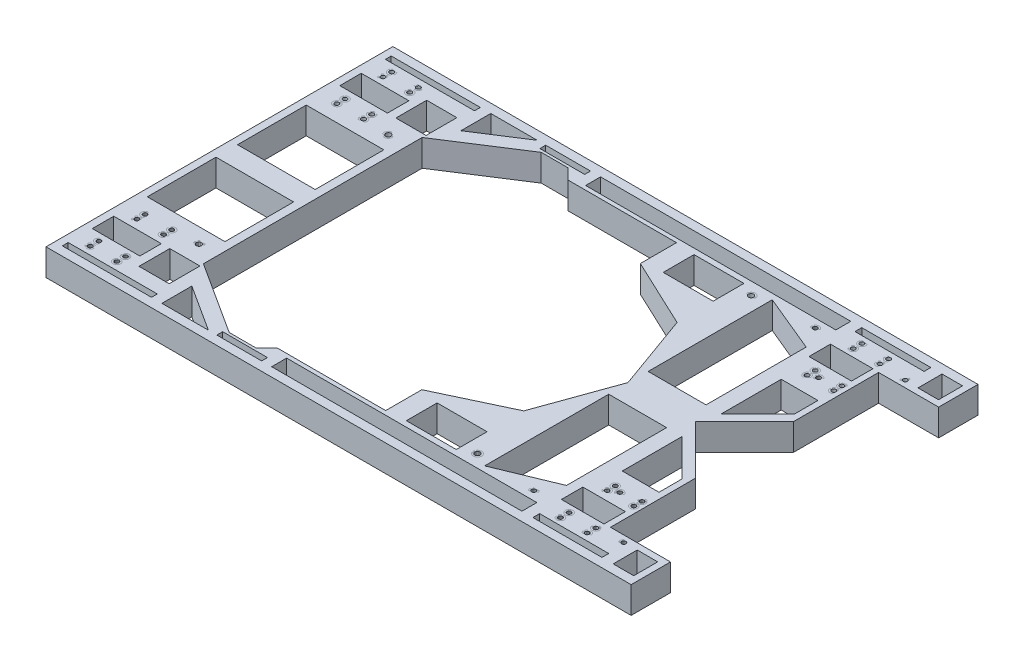
SolidWorks part; units mm, degrees
material "Magnesium Alloy"
ref_plane "Front Plane" through (0, 0, 0) normal (0, 0, 1) x (1, 0, 0)
ref_plane "Top Plane" through (0, 0, 0) normal (0, 1, 0) x (1, 0, 0)
ref_plane "Right Plane" through (0, 0, 0) normal (1, 0, 0) x (0, 0, -1)
sketch "Sketch1" plane through (0, 0, 0) normal (0, 1, 0) x (1, 0, 0)
  line L0 (0, 471.9498) -> (0, -504.9384) construction
  line L1 (-300.0375, 165.1) -> (300.0375, 165.1)
  line L2 (-300.0375, 165.1) -> (-300.0375, -165.1)
  line L3 (-300.0375, -165.1) -> (300.0375, -165.1)
  line L4 (300.0375, 165.1) -> (300.0375, -165.1)
  line L5 (-636.3607, 0) -> (748.0963, 0) construction
  dimension "D1" = 600.075
  dimension "D2" = 330.2
extrude "Boss-Extrude1" add sketch "Sketch1" along normal blind 25.4
sketch "Sketch2" plane through (-300.0375, 0, 0) normal (-1, 0, 0) x (0, 0, 1)
  line L0 (-165.1, 12.7) -> (165.1, 12.7) construction
  line L1 (-165.1, 25.4) -> (-165.1, 0) construction
  line L2 (165.1, 25.4) -> (165.1, 0) construction
  text T0 "Back" font "Century Gothic" height 19.05
extrude "Cut-Extrude1" cut sketch "Sketch2" against normal blind 2.54
sketch "Sketch3" plane through (300.0375, 0, 0) normal (1, 0, 0) x (0, 0, -1)
  line L0 (-165.1, 12.7) -> (165.1, 12.7) construction
  line L1 (-165.1, 25.4) -> (-165.1, 0) construction
  line L2 (165.1, 25.4) -> (165.1, 0) construction
  text T0 "Front" font "Century Gothic" height 19.05
extrude "Cut-Extrude2" cut sketch "Sketch3" against normal blind 2.54
sketch "Sketch4" plane through (0, 0, 0) normal (0, -1, 0) x (1, 0, 0)
  line L0 (407.1831, 0) -> (-551.8052, 0) construction
  line L1 (-113.3475, 138.43) -> (39.6875, 138.43)
  line L2 (-113.3475, 138.43) -> (-113.3475, -138.43)
  line L3 (-113.3475, -138.43) -> (39.6875, -138.43)
  line L4 (39.6875, 138.43) -> (39.6875, -138.43)
  line L5 (60.0798, 0) -> (-60.0798, 0) construction
  line L6 (-300.0375, -165.1) -> (-300.0375, 165.1) construction
  line L7 (300.0375, 165.1) -> (300.0375, -165.1) construction
  line L10 (-300.0375, 165.1) -> (300.0375, 165.1) construction
  dimension "D1" = 186.69
  dimension "D2" = 260.35
  dimension "D3" = 26.67
extrude "Cut-Extrude3" cut sketch "Sketch4" against normal up to next
ref_plane "Plane1" through (223.8375, 0, 0) normal (1, 0, 0) x (0, 0, -1)
ref_plane "Plane2" through (-223.8375, 0, 0) normal (-1, 0, 0) x (0, 0, 1)
sketch "Sketch7" plane through (0, 25.4, 0) normal (0, 1, 0) x (1, 0, 0)
  line L0 (-300.0375, -29.6562) -> (-300.0375, -165.1) construction
  line L1 (-300.0375, -165.1) -> (300.0375, -165.1) construction
  point P0 (-236.5375, -91.2978)
  point P1 (-236.5375, -135.2474)
  point P2 (-211.1375, -135.2474)
  point P3 (-211.1375, -91.2978)
  dimension "D1" = 63.5
  dimension "D2" = 63.5
  dimension "D3" = 88.9
  dimension "D4" = 88.9
  dimension "D5" = 29.8526
  dimension "D6" = 29.8526
  dimension "D7" = 43.9496
  dimension "D8" = 43.9496
hole_wizard "#21 (0.159) Diameter Hole1" positions "Sketch10" profile "Sketch11" hole size "#21" standard "ANSI Inch" end condition through all
sketch "Sketch10" plane through (0, 25.4, 0) normal (0, 1, 0) x (1, 0, 0)
  point P0 (-236.5375, -91.2978)
  point P3 (-211.1375, -91.2978)
  point P6 (-211.1375, -135.2474)
  point P9 (-236.5375, -135.2474)
sketch "Sketch11" plane through (-236.5375, 25.4, 91.2978) normal (1, 0, 0) x (0, 0, 1)
  line L0 (0, 0) -> (0, 25.4)
  line L1 (0, 25.4) -> (2.0193, 25.4)
  line L2 (2.0193, 25.4) -> (2.0193, 0)
  line L5 (2.0193, 0) -> (0, 0)
  line L11 (0, -6.35) -> (0, 107.95) construction
  dimension "Thru Hole Dia." = 4.0386
  dimension "Thru Hole Depth" = 25.4
mirror "Mirror3" about plane through (0, 0, 0) normal (1, 0, 0) of "#21 (0.159) Diameter Hole1"
mirror "Mirror4" about plane through (0, 0, 0) normal (0, 0, 1) of "Mirror3"
ref_axis "Axis1" through (-236.5375, 0, 91.2978) along (0, 1, 0)
ref_axis "Axis2" through (-211.1375, 0, 91.2978) along (0, 1, 0)
ref_axis "Axis3" through (-211.1375, 0, 135.2474) along (0, 1, 0)
ref_axis "Axis4" through (-236.5375, 0, 135.2474) along (0, 1, 0)
sketch "Sketch12" plane through (0, 25.4, 0) normal (0, 1, 0) x (1, 0, 0)
  point P0 (78.8458, -130.175)
ref_plane "Plane3" through (0, 0, 130.175) normal (0, 0, 1) x (1, 0, 0)
sketch "Sketch13" plane through (0, 0, 130.175) normal (0, 0, 1) x (1, 0, 0)
  line L0 (78.8458, 65.775) -> (78.8458, -43.461) construction
hole_wizard "Ø5.0mm Dowel Hole2" positions "Sketch16" profile "Sketch17" hole size "Ø5.0" standard "ANSI Metric" end condition through all
sketch "Sketch16" plane through (0, 25.4, 0) normal (0, 1, 0) x (1, 0, 0)
  circle A0 centre (118.8508, -130.175) radius 2.54
  circle A1 centre (118.8508, 130.175) radius 2.54
  circle A2 centre (-186.3725, 90.17) radius 2.54
  circle A3 centre (-186.3725, -90.17) radius 2.54
  point P3 (118.8508, -130.175)
  point P9 (118.8508, 130.175)
  point P12 (-186.3725, 90.17)
  point P21 (-186.3725, -90.17)
  point P24 (118.8508, -130.175)
sketch "Sketch17" plane through (118.8508, 25.4, 130.175) normal (1, 0, 0) x (0, 0, 1)
  line L0 (0, 0) -> (0, 25.4)
  line L1 (0, 25.4) -> (2.5, 25.4)
  line L2 (2.5, 25.4) -> (2.5, 0)
  line L5 (2.5, 0) -> (0, 0)
  line L11 (0, -6.35) -> (0, 107.95) construction
  dimension "Thru Hole Dia." = 5
  dimension "Thru Hole Depth" = 25.4
sketch "Sketch18" plane through (0, 25.4, 0) normal (0, 1, 0) x (1, 0, 0)
  line L0 (300.0375, 30.4067) -> (300.0375, 165.1) construction
  line L1 (300.0375, 127.635) -> (242.8875, 127.635)
  line L2 (300.0375, 127.635) -> (300.0375, -127.635)
  line L3 (300.0375, -127.635) -> (242.8875, -127.635)
  line L4 (242.8875, 127.635) -> (242.8875, -127.635)
  line L5 (300.0375, 165.1) -> (-300.0375, 165.1) construction
  line L6 (-300.0375, -165.1) -> (300.0375, -165.1) construction
  dimension "D1" = 37.465
  dimension "D2" = 37.465
  dimension "D3" = 57.15
extrude "Cut-Extrude4" cut sketch "Sketch18" against normal up to next
sketch "Sketch19" plane through (0, 25.4, 0) normal (0, -1, 0) x (-1, 0, 0)
  circle A0 centre (-218.7586, 94.615) radius 2.032
  circle A1 centre (-218.7586, 94.615) radius 2.032 construction
  circle A2 centre (-218.7586, -94.615) radius 2.032
  circle A3 centre (-218.7586, -94.615) radius 2.032 construction
  circle A4 centre (-176.2125, 133.985) radius 2.032
  circle A5 centre (-176.2125, 133.985) radius 2.032 construction
  circle A6 centre (-176.2125, -133.985) radius 2.032
  circle A7 centre (-176.2125, -133.985) radius 2.032 construction
extrude "Cut-Extrude5" cut sketch "Sketch19" along normal blind 12.7
ref_axis "Axis5" through (176.2125, 12.7, -133.985) along (0, 1, 0)
ref_axis "Axis6" through (176.2125, 12.7, 133.985) along (0, 1, 0)
ref_axis "Axis7" through (218.7586, 12.7, -94.615) along (0, 1, 0)
ref_axis "Axis8" through (218.7586, 12.7, 94.615) along (0, 1, 0)
sketch "Sketch20" plane through (0, 25.4, 0) normal (0, 1, 0) x (1, 0, 0)
  line L0 (300.0375, 165.1) -> (-300.0375, 165.1) construction
  line L1 (300.0375, 127.635) -> (300.0375, 165.1) construction
  circle A0 centre (236.5375, 143.51) radius 2.0193
  dimension "D1" = 21.59
  dimension "D2" = 63.5
extrude "Cut-Extrude6" cut sketch "Sketch20" against normal up to next
sketch "Sketch21" plane through (0, 25.4, 0) normal (0, 1, 0) x (1, 0, 0)
  line L0 (300.0375, 165.1) -> (-300.0375, 165.1) construction
  line L1 (300.0375, 127.635) -> (300.0375, 165.1) construction
  circle A0 centre (211.1375, 143.51) radius 2.0193
  circle A1 centre (211.1375, 99.06) radius 2.0193
  circle A2 centre (236.5375, 99.06) radius 2.0193
  circle A3 centre (236.5375, 143.51) radius 2.0193 construction
  dimension "D1" = 21.59
  dimension "D2" = 25.4
  dimension "D3" = 4.0386
  dimension "D4" = 44.45
  dimension "D5" = 44.45
  dimension "D6" = 63.5
  dimension "D7" = 4.0386
  dimension "D8" = 25.4
  dimension "D9" = 4.0386
extrude "Cut-Extrude7" cut sketch "Sketch21" against normal up to next
pattern_linear "LPattern1" count 2 spacing 447.675 along (-1, 0, 0) of "Cut-Extrude7", "Cut-Extrude6"
mirror "Mirror5" about plane through (0, 0, 0) normal (0, 0, 1) of "LPattern1"
sketch "Sketch22" plane through (0, 25.4, 0) normal (0, 1, 0) x (1, 0, 0)
  line L0 (300.0375, -165.1) -> (300.0375, -127.635) construction
  line L1 (160.3375, -127.635) -> (300.0375, -127.635) construction
  circle A0 centre (261.9375, -133.985) radius 2.032
  dimension "D1" = 4.064
  dimension "D2" = 38.1
  dimension "D3" = 6.35
extrude "Cut-Extrude8" cut sketch "Sketch22" against normal up to next
mirror "Mirror6" about plane through (0, 0, 0) normal (0, 0, 1) of "Cut-Extrude8"
sketch "Sketch23" plane through (0, 25.4, 0) normal (0, 1, 0) x (1, 0, 0)
  circle A0 centre (-236.5375, 143.51) radius 2.0193
  circle A1 centre (-236.5375, 143.51) radius 3.6068
  circle A2 centre (-211.1375, 143.51) radius 2.0193
  circle A3 centre (-211.1375, 143.51) radius 3.6068
  circle A4 centre (-236.5375, 135.2474) radius 2.0193
  circle A5 centre (-236.5375, 135.2474) radius 3.6068
  circle A6 centre (-211.1375, 135.2474) radius 2.0193
  circle A7 centre (-211.1375, 135.2474) radius 3.6068
  circle A8 centre (-236.5375, 99.06) radius 2.0193
  circle A9 centre (-236.5375, 99.06) radius 3.6068
  circle A10 centre (-236.5375, 91.2978) radius 2.0193
  circle A11 centre (-236.5375, 91.2978) radius 3.6068
  circle A12 centre (-211.1375, 99.06) radius 2.0193
  circle A13 centre (-211.1375, 99.06) radius 3.6068
  circle A14 centre (-211.1375, 91.2978) radius 2.0193
  circle A15 centre (-211.1375, 91.2978) radius 3.6068
  circle A16 centre (-186.3725, 90.17) radius 2.5006
  circle A17 centre (-186.3725, 90.17) radius 4.0881
  circle A18 centre (118.8508, 130.175) radius 2.5006
  circle A19 centre (118.8508, 130.175) radius 4.0881
  circle A20 centre (176.2125, 133.985) radius 2.032
  circle A21 centre (211.1375, 99.06) radius 2.0193
  circle A22 centre (211.1375, 91.2978) radius 2.0193
  circle A23 centre (218.7586, 94.615) radius 2.032
  circle A24 centre (211.1375, 135.2474) radius 2.0193
  circle A25 centre (211.1375, 143.51) radius 2.0193
  circle A26 centre (236.5375, 143.51) radius 2.0193
  circle A27 centre (236.5375, 135.2474) radius 2.0193
  circle A28 centre (236.5375, 99.06) radius 2.0193
  circle A29 centre (236.5375, 91.2978) radius 2.0193
  circle A30 centre (261.9375, 133.985) radius 2.032
  circle A31 centre (176.2125, 133.985) radius 3.6195
  circle A32 centre (211.1375, 143.51) radius 3.6068
  circle A33 centre (211.1375, 135.2474) radius 3.6068
  circle A34 centre (211.1375, 99.06) radius 3.6068
  circle A35 centre (211.1375, 91.2978) radius 3.6068
  circle A36 centre (218.7586, 94.615) radius 3.6195
  circle A37 centre (236.5375, 91.2978) radius 3.6068
  circle A38 centre (236.5375, 99.06) radius 3.6068
  circle A39 centre (236.5375, 135.2474) radius 3.6068
  circle A40 centre (236.5375, 143.51) radius 3.6068
  circle A41 centre (261.9375, 133.985) radius 3.6195
  dimension "D1" = 1.5875
  dimension "D2" = 1.5875
  dimension "D3" = 1.5875
  dimension "D4" = 1.5875
  dimension "D5" = 1.5875
  dimension "D6" = 1.5875
  dimension "D7" = 1.5875
  dimension "D8" = 1.5875
  dimension "D9" = 1.5875
  dimension "D10" = 4.0386
  dimension "D11" = 4.0386
  dimension "D12" = 4.0386
  dimension "D13" = 4.0386
  dimension "D14" = 5.0013
  dimension "D15" = 4.0386
  dimension "D16" = 4.0386
  dimension "D17" = 4.0386
  dimension "D18" = 4.0386
  dimension "D19" = 1.5875
  dimension "D20" = 4.064
  dimension "D21" = 1.5875
  dimension "D22" = 1.5875
  dimension "D23" = 1.5875
  dimension "D24" = 1.5875
  dimension "D25" = 1.5875
  dimension "D26" = 1.5875
  dimension "D27" = 1.5875
  dimension "D28" = 1.5875
  dimension "D29" = 1.5875
  dimension "D30" = 1.5875
  dimension "D31" = 1.5875
  dimension "D32" = 5.0013
  dimension "D33" = 4.0386
  dimension "D34" = 4.0386
  dimension "D35" = 4.064
  dimension "D36" = 4.0386
  dimension "D37" = 4.0386
  dimension "D38" = 4.0386
  dimension "D39" = 4.0386
  dimension "D40" = 4.0386
  dimension "D41" = 4.0386
  dimension "D42" = 4.064
extrude "Boss-Extrude2" add sketch "Sketch23" against normal up to surface (25.4 mm away) separate body up to face at (261.9375, 0, -131.953)
mirror "Mirror9" about plane through (0, 0, 0) normal (0, 0, 1) of bodies 128 130 127 131 125 123 124 126 136 137 139 140 142 141 143 134 135 133 132 138 129
sketch "Sketch24" plane through (0, 25.4, 0) normal (0, 1, 0) x (1, 0, 0)
  line L0 (-256.9969, 165.1) -> (-256.9969, 66.04)
  line L1 (-256.9969, 66.04) -> (-168.0969, 66.04)
  line L2 (-168.0969, 66.04) -> (-168.0969, 104.14)
  line L3 (-168.0969, 104.14) -> (-99.1707, 148.5171)
  line L4 (-99.1707, 148.5171) -> (-73.7707, 148.5171)
  line L5 (-73.7707, 148.5171) -> (-63.6526, 138.43)
  line L6 (-63.6526, 138.43) -> (39.5764, 138.43)
  line L7 (39.5764, 138.43) -> (39.5764, 104.0777)
  line L8 (39.5764, 104.0777) -> (105.7193, 72.9194)
  line L9 (105.7193, 72.9194) -> (131.9374, 0)
  line L10 (176.5339, 0) -> (-283.2885, 0) construction
  line L11 (105.7193, -72.9194) -> (131.9374, 0)
  line L12 (39.5764, -104.0777) -> (105.7193, -72.9194)
  line L13 (39.5764, -138.43) -> (39.5764, -104.0777)
  line L14 (-63.6526, -138.43) -> (39.5764, -138.43)
  line L15 (-73.7707, -148.5171) -> (-63.6526, -138.43)
  line L16 (-99.1707, -148.5171) -> (-73.7707, -148.5171)
  line L17 (-168.0969, -104.14) -> (-99.1707, -148.5171)
  line L18 (-168.0969, -66.04) -> (-168.0969, -104.14)
  line L19 (-256.9969, -66.04) -> (-168.0969, -66.04)
  line L20 (-256.9969, -165.1) -> (-256.9969, -66.04)
  line L21 (-256.9969, 165.1) -> (-300.0375, 165.1)
  line L22 (-300.0375, 165.1) -> (-300.0375, -165.1)
  line L23 (-300.0375, -165.1) -> (-256.9969, -165.1)
  line L24 (242.8875, 46.4819) -> (196.2944, 0)
  line L25 (242.8875, -46.4819) -> (196.2944, 0)
  line L26 (300.0375, 165.1) -> (-300.0375, 165.1) construction
  line L27 (-300.0375, 165.1) -> (-300.0375, -165.1) construction
  line L28 (242.8875, 127.635) -> (242.8875, -127.635) construction
  line L29 (-60.0798, 0) -> (60.0798, 0) construction
  line L30 (242.8875, 46.4819) -> (242.8875, -46.4819)
  dimension "D1" = 88.9
  dimension "D2" = 99.06
  dimension "D3" = 38.1
  dimension "D4" = 25.4
extrude "Cut-Extrude9" cut sketch "Sketch24" against normal blind 25.4
sketch "Sketch25" plane through (0, 25.4, 0) normal (0, 1, 0) x (1, 0, 0)
  line L1 (-256.9969, 66.04) -> (-168.0969, 66.04)
  line L2 (-256.9969, 66.04) -> (-256.9969, -66.04)
  line L3 (-256.9969, -66.04) -> (-168.0969, -66.04)
  line L4 (-168.0969, 66.04) -> (-168.0969, -66.04)
extrude "Boss-Extrude3" add sketch "Sketch25" against normal up to surface (25.4 mm away) up to face at (261.9375, 0, -131.953)
sketch "Sketch26" plane through (0, 25.4, 0) normal (0, 1, 0) x (1, 0, 0)
  line L0 (-155.2354, -128.0511) -> (-110.9798, -156.5444)
  line L1 (132.3591, -18.7684) -> (187.4853, -18.7684)
  line L2 (132.3591, -18.7684) -> (132.3591, -114.0643)
  line L4 (187.4853, -18.7684) -> (187.4853, -114.0643)
  line L5 (57.8801, -107.6134) -> (105.3825, -107.6134)
  line L6 (57.8801, -107.6134) -> (57.8801, -136.9358)
  line L7 (57.8801, -136.9358) -> (105.3825, -136.9358)
  line L8 (105.3825, -107.6134) -> (105.3825, -136.9358)
  line L9 (-196.6386, -107.6134) -> (-167.9027, -107.6134)
  line L10 (-196.6386, -107.6134) -> (-196.6386, -136.9358)
  line L11 (-196.6386, -136.9358) -> (-167.9027, -136.9358)
  line L12 (-167.9027, -107.6134) -> (-167.9027, -136.9358)
  line L13 (-250.0055, -10.2629) -> (-176.1129, -10.2629)
  line L14 (-250.0055, -10.2629) -> (-250.0055, -75.6519)
  line L15 (-250.0055, -75.6519) -> (-176.1129, -75.6519)
  line L16 (-176.1129, -10.2629) -> (-176.1129, -75.6519)
  line L17 (-110.9798, -156.5444) -> (-155.2354, -156.5444)
  line L18 (-155.2354, -156.5444) -> (-155.2354, -128.0511)
  line L19 (-50.7302, -142.2978) -> (187.4853, -142.2978)
  line L20 (187.4853, -142.2978) -> (187.4853, -156.5444)
  line L21 (187.4853, -156.5444) -> (-50.7302, -156.5444)
  line L22 (-50.7302, -156.5444) -> (-50.7302, -142.2978)
  line L23 (132.3591, -114.0643) -> (132.3591, -136.9358)
  line L24 (132.3591, -136.9358) -> (187.4853, -114.0643)
  line L25 (202.1465, -18.7684) -> (237.1125, -53.7344)
  line L26 (237.1125, -53.7344) -> (237.1125, -75.6519)
  line L27 (237.1125, -75.6519) -> (202.1465, -75.6519)
  line L28 (202.1465, -75.6519) -> (202.1465, -18.7684)
  line L30 (196.596, -107.6134) -> (237.1125, -107.6134)
  line L31 (196.596, -107.6134) -> (196.596, -128.0511)
  line L32 (196.596, -128.0511) -> (237.1125, -128.0511)
  line L33 (237.1125, -107.6134) -> (237.1125, -128.0511)
  line L34 (274.3669, -133.646) -> (293.9207, -133.646)
  line L35 (274.3669, -133.646) -> (274.3669, -156.5444)
  line L36 (274.3669, -156.5444) -> (293.9207, -156.5444)
  line L37 (293.9207, -133.646) -> (293.9207, -156.5444)
  line L38 (197.9292, -150.089) -> (263.7011, -150.089)
  line L39 (197.9292, -150.089) -> (197.9292, -156.5444)
  line L40 (197.9292, -156.5444) -> (263.7011, -156.5444)
  line L41 (263.7011, -150.089) -> (263.7011, -156.5444)
  line L42 (-250.0055, -107.6134) -> (-204.7018, -107.6134)
  line L43 (-250.0055, -107.6134) -> (-250.0055, -128.0511)
  line L44 (-250.0055, -128.0511) -> (-204.7018, -128.0511)
  line L45 (-204.7018, -107.6134) -> (-204.7018, -128.0511)
  line L46 (-250.0055, -150.9778) -> (-165.1497, -150.9778)
  line L47 (-250.0055, -150.9778) -> (-250.0055, -156.5444)
  line L48 (-250.0055, -156.5444) -> (-165.1497, -156.5444)
  line L49 (-165.1497, -150.9778) -> (-165.1497, -156.5444)
  line L50 (-102.933, -150.9778) -> (-60.2701, -150.9778)
  line L51 (-102.933, -150.9778) -> (-102.933, -156.5444)
  line L52 (-102.933, -156.5444) -> (-60.2701, -156.5444)
  line L53 (-60.2701, -150.9778) -> (-60.2701, -156.5444)
extrude "Cut-Extrude10" cut sketch "Sketch26" against normal up to next (25.4 mm away)
mirror "Mirror10" about plane through (0, 0, 0) normal (0, 0, 1) of "Cut-Extrude10"
